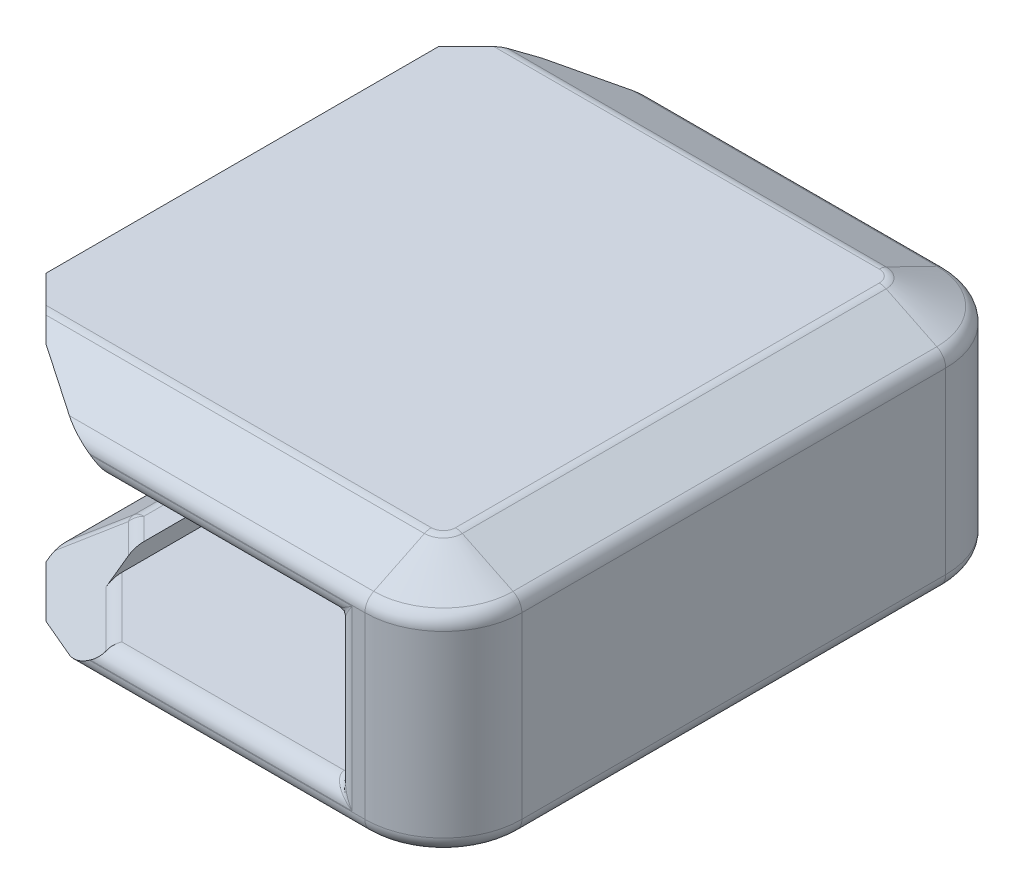
SolidWorks part; units mm, degrees
ref_plane "Front Plane" through (0, 0, 0) normal (0, 0, 1) x (1, 0, 0)
ref_plane "Top Plane" through (0, 0, 0) normal (0, 1, 0) x (1, 0, 0)
ref_plane "Right Plane" through (0, 0, 0) normal (1, 0, 0) x (0, 0, -1)
sketch "Sketch1" plane through (0, 0, 0) normal (0, 0, 1) x (1, 0, 0)
  line L0 (0, 0) -> (-150.7043, 0) construction
  line L1 (0, -1.86) -> (0, 1.86)
  line L2 (0, 1.86) -> (-7.4, 1.86)
  line L3 (-7.4, 1.86) -> (-7.4, 1.46)
  line L4 (-7.4, 1.46) -> (-8.1, 1.46)
  line L5 (-8.1, 1.46) -> (-9.8, 2.8506)
  line L6 (-9.8, 2.8506) -> (-9.8, 3.31)
  line L7 (-9.8, 3.31) -> (2.7266, 3.31)
  line L8 (2.7266, 3.31) -> (2.7266, -3.31)
  line L10 (-9.8, -3.31) -> (2.7266, -3.31)
  line L11 (-9.8, -2.8506) -> (-9.8, -3.31)
  line L12 (-8.1, -1.46) -> (-9.8, -2.8506)
  line L13 (-7.4, -1.46) -> (-8.1, -1.46)
  line L14 (-7.4, -1.86) -> (-7.4, -1.46)
  line L15 (0, -1.86) -> (-7.4, -1.86)
  dimension "D1" = 1.86
  dimension "D2" = 0.4
  dimension "D3" = 0.7
  dimension "D4" = 7.4
  dimension "D6" = 2.4
extrude "Boss-Extrude1" add sketch "Sketch1" along normal blind 14.8
chamfer "Chamfer1" distance 2.4 angle 45 4 edges at (-9.8, 3.0803, 0) (-9.8, -3.0803, 0) (-9.8, -3.0803, 14.8) (-9.8, 3.0803, 14.8)
chamfer "Chamfer2" distance 1.6 angle 45 4 edges at (-7.75, 1.46, 14.45) (-7.75, -1.46, 14.45) (-7.75, 1.46, 0.35) (-7.75, -1.46, 0.35)
fillet "Fillet2" radius 2 2 edges at (2.7266, 0, 0) (2.7266, 0, 14.8)
chamfer "Chamfer3" distance 1.6 angle 26 10 edges at (-3.3367, 3.31, 0) (2.1408, 3.31, 0.5858) (2.7266, 3.31, 7.4) (2.1408, 3.31, 14.2142) (-3.3367, 3.31, 14.8) (-3.3367, -3.31, 0) (2.1408, -3.31, 0.5858) (2.7266, -3.31, 7.4) (2.1408, -3.31, 14.2142) (-3.3367, -3.31, 14.8) first distance on face at (-3.3331, 3.31, 7.4) first distance on face at (-3.3331, -3.31, 7.4)
fillet "Fillet3" radius 0.4 32 edges at (-2.9617, 2.5296, 14.8) (2.1408, 2.5296, 14.2142) (2.7266, 2.5296, 7.4) (2.1408, 2.5296, 0.5858) (-2.9617, -2.5296, 14.8) (2.1408, -2.5296, 14.2142) (2.7266, -2.5296, 7.4) (2.1408, -2.5296, 0.5858) (-2.9617, 2.5296, 0) (-2.8515, 1.86, 0) (0, 0, 0) (-2.8515, -1.86, 0) (-2.9617, -2.5296, 0) (-6.5515, -1.86, 0.8485) (-7.75, -1.46, 2.6127) (-8.95, -2.1553, 2.8295) (-8.95, 2.1553, 2.8295) (-7.75, 1.46, 2.6127) (-6.5515, 1.86, 0.8485) (-6.5515, 1.86, 13.9515) (-7.75, 1.46, 12.1873) (-8.95, 2.1553, 11.9705) (-8.95, -2.1553, 11.9705) (-7.75, -1.46, 12.1873) (-6.5515, -1.86, 13.9515) (-8.1, -1.46, 7.4) (-8.1, 1.46, 7.4) (-9.8, 2.8506, 7.4) (-9.8, -2.8506, 7.4) (-2.8515, -1.86, 14.8) (0, 0, 14.8) (-2.8515, 1.86, 14.8)
fillet "Fillet4" radius 0.4 10 edges at (-4.1367, -3.31, 13.2) (1.0095, -3.31, 13.0828) (1.1266, -3.31, 7.4) (1.0095, -3.31, 1.7172) (-4.1367, 3.31, 13.2) (1.0095, 3.31, 13.0828) (1.1266, 3.31, 7.4) (1.0095, 3.31, 1.7172) (-4.1367, -3.31, 1.6) (-4.1367, 3.31, 1.6)
fillet "Fillet5" radius 0.2 6 edges at (0.1172, -1.9772, 14.6828) (0.1172, -1.9772, 0.1172) (0.1172, 1.9772, 14.6828) (0.1172, 1.9772, 0.1172) (0, -1.86, 7.4) (0, 1.86, 7.4)
